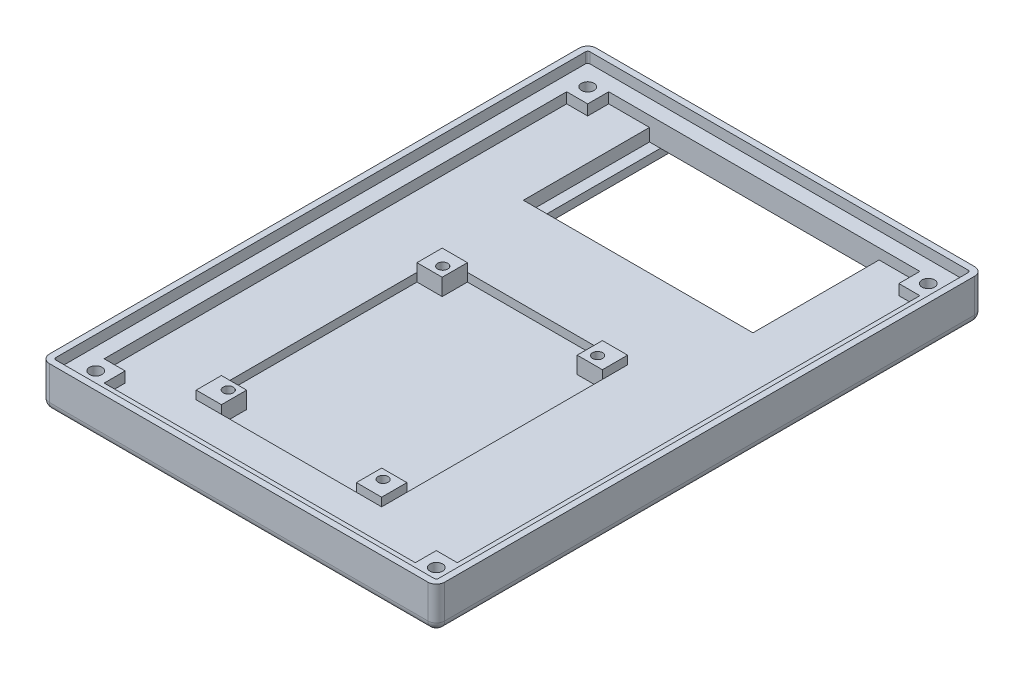
SolidWorks part; units mm, degrees
ref_plane "Front Plane" through (0, 0, 0) normal (0, 0, 1) x (1, 0, 0)
ref_plane "Top Plane" through (0, 0, 0) normal (0, 1, 0) x (1, 0, 0)
ref_plane "Right Plane" through (0, 0, 0) normal (1, 0, 0) x (0, 0, -1)
sketch "Sketch1" plane through (0, 0, 0) normal (0, 1, 0) x (1, 0, 0)
  line L1 (0, 0) -> (94, 0)
  line L2 (0, 0) -> (0, 130)
  line L3 (0, 130) -> (94, 130)
  line L4 (94, 0) -> (94, 130)
  dimension "D1" = 94
  dimension "D2" = 130
extrude "Boss-Extrude1" add sketch "Sketch1" along normal blind 5
sketch "Sketch2" plane through (0, 5, 0) normal (0, 1, 0) x (1, 0, 0)
  line L4 (5, 125) -> (5, 5)
  line L5 (5, 5) -> (89, 5)
  line L6 (89, 5) -> (89, 125)
  line L7 (89, 125) -> (5, 125)
  line L8 (0, 130) -> (0, 0)
  line L9 (0, 0) -> (94, 0)
  line L10 (94, 0) -> (94, 130)
  line L11 (94, 130) -> (0, 130)
  line L12 (0, 130) -> (0, 0)
  line L13 (0, 0) -> (94, 0)
  line L14 (94, 0) -> (94, 130)
  line L15 (94, 130) -> (0, 130)
  dimension "D1" = 0
  dimension "D2" = 5
extrude "Boss-Extrude2" add sketch "Sketch2" along normal blind 5
fillet "Fillet1" radius 2 8 edges at (0, 5, -130) (0, 5, 0) (94, 5, 0) (47, 0, 0) (0, 0, -65) (94, 0, -65) (47, 0, -130) (94, 5, -130)
sketch "Sketch3" plane through (0, 5, 0) normal (0, 1, 0) x (1, 0, 0)
  line L0 (5, 125) -> (5, 5) construction
  line L1 (21.9, 73.5) -> (66, 73.5)
  line L2 (21.9, 73.5) -> (21.9, 15)
  line L3 (21.9, 15) -> (66, 15)
  line L4 (66, 73.5) -> (66, 15)
  line L11 (5, 5) -> (89, 5) construction
  dimension "D1" = 58.5
  dimension "D2" = 44.1
  dimension "D3" = 16.9
  dimension "D4" = 10
extrude "Cut-Extrude1" cut sketch "Sketch3" against normal blind 2
sketch "Sketch5" plane through (0, 3, 0) normal (0, 1, 0) x (1, 0, 0)
  line L0 (66, 73.5) -> (21.9, 73.5) construction
  line L1 (21.9, 73.5) -> (27.9, 73.5)
  line L2 (21.9, 73.5) -> (21.9, 67.5)
  line L3 (21.9, 67.5) -> (27.9, 67.5)
  line L4 (27.9, 73.5) -> (27.9, 67.5)
  line L5 (60, 73.5) -> (66, 73.5)
  line L6 (60, 73.5) -> (60, 67.5)
  line L7 (60, 67.5) -> (66, 67.5)
  line L8 (66, 73.5) -> (66, 67.5)
  line L9 (60, 21) -> (66, 21)
  line L10 (60, 21) -> (60, 15)
  line L11 (60, 15) -> (66, 15)
  line L12 (66, 21) -> (66, 15)
  line L13 (21.9, 21) -> (27.9, 21)
  line L14 (21.9, 21) -> (21.9, 15)
  line L15 (21.9, 15) -> (27.9, 15)
  line L16 (27.9, 21) -> (27.9, 15)
  line L17 (21.9, 73.5) -> (21.9, 15) construction
  line L18 (66, 15) -> (66, 73.5) construction
  line L19 (21.9, 15) -> (66, 15) construction
  dimension "D1" = 6
  dimension "D2" = 6
  dimension "D3" = 6
  dimension "D4" = 6
  dimension "D5" = 6
  dimension "D6" = 6
  dimension "D7" = 6
  dimension "D8" = 6
extrude "Boss-Extrude4" add sketch "Sketch5" along normal blind 4
sketch "Sketch7" plane through (0, 7, 0) normal (0, 1, 0) x (1, 0, 0)
  circle A0 centre (25.6846, 69.839) radius 1.2
  circle A1 centre (62.5146, 69.839) radius 1.2
  circle A2 centre (62.5146, 18.8358) radius 1.2
  circle A3 centre (25.6846, 18.8358) radius 1.2
extrude "Cut-Extrude2" cut sketch "Sketch7" against normal blind 3
sketch "Sketch8" plane through (0, 5, 0) normal (0, 1, 0) x (1, 0, 0)
  line L1 (19.7, 95) -> (74.3, 95)
  line L2 (19.7, 95) -> (19.7, 125)
  line L3 (19.7, 125) -> (74.3, 125)
  line L4 (74.3, 95) -> (74.3, 125)
  line L5 (89, 125) -> (5, 125) construction
  line L6 (89, 125) -> (5, 125) construction
  point P4 (47, 125)
  point P9 (47, 95)
  dimension "D1" = 30
  dimension "D2" = 54.6
extrude "Cut-Extrude3" cut sketch "Sketch8" against normal blind 3
sketch "Sketch9" plane through (0, 2, 0) normal (0, 1, 0) x (1, 0, 0)
  line L0 (19.7, 95) -> (74.3, 95) construction
  line L1 (22.3, 96.5) -> (71.7, 96.5)
  line L2 (22.3, 96.5) -> (22.3, 123.5)
  line L3 (22.3, 123.5) -> (71.7, 123.5)
  line L4 (71.7, 96.5) -> (71.7, 123.5)
  line L5 (74.3, 125) -> (19.7, 125) construction
  line L6 (19.7, 125) -> (19.7, 95) construction
  line L7 (74.3, 95) -> (74.3, 125) construction
  dimension "D1" = 1.5
  dimension "D2" = 1.5
  dimension "D3" = 2.6
  dimension "D4" = 2.6
extrude "Cut-Extrude4" cut sketch "Sketch9" against normal blind 2
sketch "Sketch10" plane through (0, 0, 0) normal (0, -1, 0) x (1, 0, 0)
  line L1 (71.7, -123.5) -> (22.3, -123.5)
  line L2 (71.7, -123.5) -> (71.7, -130.1195)
  line L3 (71.7, -130.1195) -> (22.3, -130.1195)
  line L4 (22.3, -123.5) -> (22.3, -130.1195)
  line L5 (22.3, -123.5) -> (22.3, -96.5) construction
  line L6 (71.7, -96.5) -> (71.7, -123.5) construction
  line L7 (71.7, -123.5) -> (22.3, -123.5) construction
extrude "Cut-Extrude5" cut sketch "Sketch10" against normal blind 2
sketch "Sketch11" plane through (0, 0, -96.5) normal (0, 0, -1) x (-1, 0, 0)
  line L0 (-22.3, 0) -> (-71.7, 0) construction
  line L1 (-49.5, 1.5) -> (-44.5, 1.5)
  line L2 (-49.5, 1.5) -> (-49.5, 0.5)
  line L3 (-49.5, 0.5) -> (-44.5, 0.5)
  line L4 (-44.5, 1.5) -> (-44.5, 0.5)
  line L5 (-71.7, 0) -> (-71.7, 2) construction
  point P6 (-47, 0)
  point P7 (-47, 0.5)
  point P10 (-71.7, 1)
  point P11 (-49.5, 1)
  dimension "D1" = 5
  dimension "D2" = 1
extrude "Cut-Extrude6" cut sketch "Sketch11" against normal blind 3
sketch "Sketch14" plane through (0, 10, 0) normal (0, 1, 0) x (1, 0, 0)
  line L8 (89, 5) -> (89, 125)
  line L9 (89, 125) -> (5, 125)
  line L10 (5, 125) -> (5, 5)
  line L11 (5, 5) -> (89, 5)
  line L12 (89, 5) -> (89, 125)
  line L13 (89, 125) -> (5, 125)
  line L14 (5, 125) -> (5, 5)
  line L15 (5, 5) -> (89, 5)
  line L20 (92.5, 2) -> (92.5, 128)
  line L21 (92, 128.5) -> (2, 128.5)
  line L22 (1.5, 128) -> (1.5, 2)
  line L23 (2, 1.5) -> (92, 1.5)
  line L24 (92.5, 2) -> (92.5, 128)
  line L25 (92, 128.5) -> (2, 128.5)
  line L26 (1.5, 128) -> (1.5, 2)
  line L27 (2, 1.5) -> (92, 1.5)
  arc A12 (92.5, 128) -> (92, 128.5) centre (92, 128) ccw
  arc A13 (2, 128.5) -> (1.5, 128) centre (2, 128) ccw
  arc A14 (1.5, 2) -> (2, 1.5) centre (2, 2) ccw
  arc A15 (92, 1.5) -> (92.5, 2) centre (92, 2) ccw
  arc A16 (92.5, 128) -> (92, 128.5) centre (92, 128) ccw
  arc A17 (2, 128.5) -> (1.5, 128) centre (2, 128) ccw
  arc A18 (1.5, 2) -> (2, 1.5) centre (2, 2) ccw
  arc A19 (92, 1.5) -> (92.5, 2) centre (92, 2) ccw
  dimension "D1" = 5
  dimension "D2" = 1.5
extrude "Cut-Extrude8" cut sketch "Sketch14" against normal blind 2.5
sketch "Sketch15" plane through (0, 5, 0) normal (0, 1, 0) x (1, 0, 0)
  line L1 (89, 120) -> (84, 120)
  line L2 (89, 120) -> (89, 125)
  line L3 (89, 125) -> (84, 125)
  line L4 (84, 120) -> (84, 125)
  line L5 (10, 120) -> (5, 120)
  line L6 (10, 120) -> (10, 125)
  line L7 (10, 125) -> (5, 125)
  line L8 (5, 120) -> (5, 125)
  line L9 (10, 5) -> (5, 5)
  line L10 (10, 5) -> (10, 10)
  line L11 (10, 10) -> (5, 10)
  line L12 (5, 5) -> (5, 10)
  line L13 (89, 5) -> (84, 5)
  line L14 (89, 5) -> (89, 10)
  line L15 (89, 10) -> (84, 10)
  line L16 (84, 5) -> (84, 10)
  line L17 (89, 125) -> (74.3, 125) construction
  line L18 (89, 5) -> (89, 125) construction
  line L19 (19.7, 125) -> (5, 125) construction
  line L20 (5, 125) -> (5, 5) construction
  line L22 (5, 5) -> (89, 5) construction
  dimension "D1" = 5
  dimension "D2" = 5
  dimension "D3" = 5
  dimension "D4" = 5
  dimension "D5" = 5
  dimension "D6" = 5
  dimension "D7" = 5
  dimension "D8" = 5
extrude "Boss-Extrude5" add sketch "Sketch15" along normal blind 2.5
sketch "Sketch16" plane through (0, 7.5, 0) normal (0, 1, 0) x (1, 0, 0)
  line L0 (10, 120) -> (10, 125) construction
  line L2 (5, 120) -> (10, 120) construction
  line L4 (84, 125) -> (84, 120) construction
  line L5 (89, 10) -> (84, 10) construction
  circle A0 centre (6.5, 123.5) radius 1.5
  circle A1 centre (87.5, 123.5) radius 1.5
  circle A2 centre (87.5, 6.5) radius 1.5
  circle A3 centre (6.5, 6.5) radius 1.5
  point P0 (6.5, 123.5)
  point P1 (87.5, 123.5)
  point P2 (87.5, 6.5)
  point P3 (6.5, 6.5)
  dimension "D5" = 3
  dimension "D6" = 3
  dimension "D7" = 3
  dimension "D8" = 3
  dimension "D1" = 3.5
  dimension "D2" = 3.5
  dimension "D3" = 3.5
  dimension "D4" = 3.5
extrude "Cut-Extrude9" cut sketch "Sketch16" against normal through all
sketch "Sketch17" plane through (0, 0, 0) normal (0, -1, 0) x (1, 0, 0)
  circle A0 centre (6.5, -6.5) radius 2.8
  circle A1 centre (87.5, -6.5) radius 2.8
  circle A2 centre (87.5, -123.5) radius 2.8
  circle A3 centre (6.5, -123.5) radius 2.8
  dimension "D1" = 5.6
  dimension "D2" = 5.6
  dimension "D3" = 5.6
  dimension "D4" = 5.6
extrude "Cut-Extrude10" cut sketch "Sketch17" against normal blind 3
sketch "Sketch18" plane through (0, 0, 0) normal (0, -1, 0) x (1, 0, 0)
  circle A0 centre (6.5, -123.5) radius 4
  circle A1 centre (87.5, -123.5) radius 4
  circle A2 centre (87.5, -6.5) radius 4
  circle A3 centre (6.5, -6.5) radius 4
  circle A4 centre (87.5, -123.5) radius 2.8 construction
  circle A5 centre (6.5, -123.5) radius 2.8 construction
  circle A6 centre (6.5, -6.5) radius 2.8 construction
  circle A7 centre (87.5, -6.5) radius 2.8 construction
  point P8 (0, 0)
  dimension "D1" = 8
  dimension "D2" = 8
  dimension "D3" = 8
  dimension "D4" = 8
extrude "Cut-Extrude11" cut sketch "Sketch18" against normal blind 2
